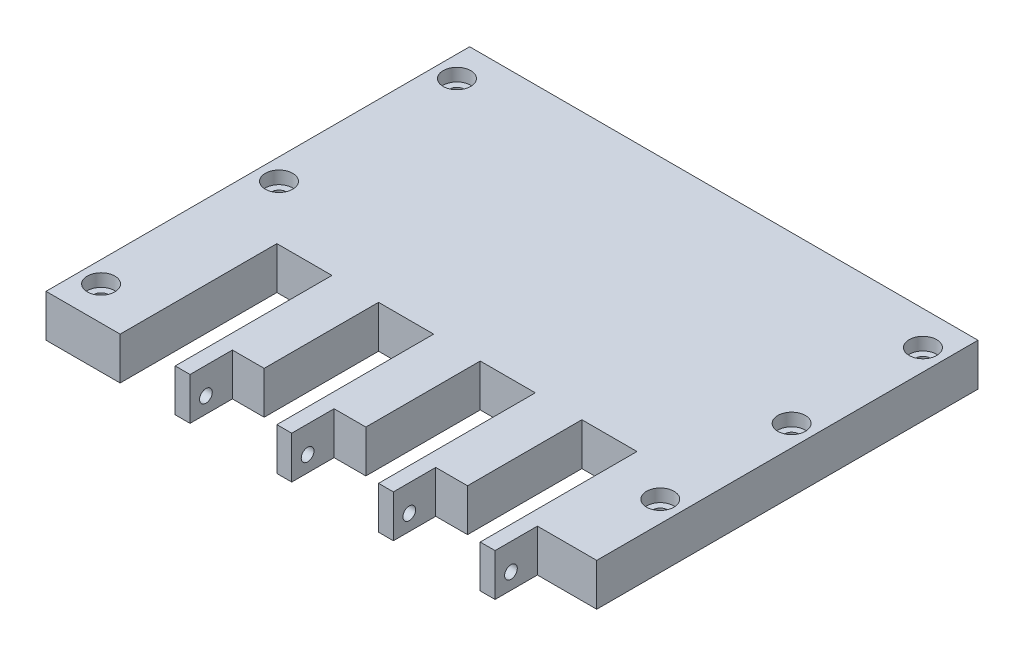
SolidWorks part; units mm, degrees
ref_plane "Front Plane" through (0, 0, 0) normal (0, 0, 1) x (1, 0, 0)
ref_plane "Top Plane" through (0, 0, 0) normal (0, 1, 0) x (1, 0, 0)
ref_plane "Right Plane" through (0, 0, 0) normal (1, 0, 0) x (0, 0, -1)
sketch "Sketch1" plane through (0, 0, 0) normal (0, 1, 0) x (1, 0, 0)
  line L1 (60, -50) -> (-60, -50)
  line L2 (60, -50) -> (60, 50)
  line L3 (60, 50) -> (-60, 50)
  line L4 (-60, -50) -> (-60, 50)
  line L5 (60, -50) -> (-60, 50) construction
  line L6 (60, 50) -> (-60, -50) construction
  point P0 (0, 0)
  dimension "D1" = 120
  dimension "D2" = 100
extrude "Boss-Extrude1" add sketch "Sketch1" along normal blind 10 contours L3 L1 | L3 L4 L1 | L3 L1 L2 region at (0, 0, 0)
sketch "Sketch2" plane through (0, 0, 50) normal (0, 0, 1) x (1, 0, 0)
  line L0 (-60, 0) -> (60, 0) construction
  line L1 (60, 10) -> (-60, 10) construction
  line L4 (-29.5, -10) -> (-42.5, -10)
  line L5 (-29.5, -10) -> (-29.5, 10)
  line L6 (-29.5, 10) -> (-42.5, 10)
  line L7 (-42.5, -10) -> (-42.5, 10)
  line L8 (-29.5, -10) -> (-42.5, 10) construction
  line L9 (-29.5, 10) -> (-42.5, -10) construction
  line L10 (-5.5, -10) -> (-18.5, -10)
  line L11 (-5.5, -10) -> (-5.5, 10)
  line L12 (-5.5, 10) -> (-18.5, 10)
  line L13 (-18.5, -10) -> (-18.5, 10)
  line L14 (-5.5, -10) -> (-18.5, 10) construction
  line L15 (-5.5, 10) -> (-18.5, -10) construction
  line L16 (18.5, -10) -> (5.5, -10)
  line L17 (18.5, -10) -> (18.5, 10)
  line L18 (18.5, 10) -> (5.5, 10)
  line L19 (5.5, -10) -> (5.5, 10)
  line L20 (18.5, -10) -> (5.5, 10) construction
  line L21 (18.5, 10) -> (5.5, -10) construction
  line L22 (42.5, -10) -> (29.5, -10)
  line L23 (42.5, -10) -> (42.5, 10)
  line L24 (42.5, 10) -> (29.5, 10)
  line L25 (29.5, -10) -> (29.5, 10)
  line L26 (42.5, -10) -> (29.5, 10) construction
  line L27 (42.5, 10) -> (29.5, -10) construction
  line L29 (60, 0) -> (-60, 0) construction
  point P7 (-36, 0)
  point P8 (-12, 0)
  point P9 (12, 0)
  point P10 (36, 0)
  point P11 (-36, 0)
  point P16 (-12, 0)
  point P21 (12, 0)
  point P26 (36, 0)
  point P33 (0, 0)
  dimension "D1" = 120
  dimension "D3" = 13
extrude "Cut-Extrude1" cut sketch "Sketch2" against normal blind 37
sketch "Sketch3" plane through (0, 0, 50) normal (0, 0, 1) x (1, 0, 0)
  line L0 (60, 10) -> (60, 0) construction
  line L1 (-18.5, 0) -> (-26, 0)
  line L2 (-18.5, 0) -> (-18.5, 10)
  line L3 (-18.5, 10) -> (-26, 10)
  line L4 (-26, 0) -> (-26, 10)
  line L5 (5.5, 0) -> (-2, 0)
  line L6 (5.5, 0) -> (5.5, 10)
  line L7 (5.5, 10) -> (-2, 10)
  line L8 (-2, 0) -> (-2, 10)
  line L9 (29.5, 0) -> (22, 0)
  line L10 (29.5, 0) -> (29.5, 10)
  line L11 (29.5, 10) -> (22, 10)
  line L12 (22, 0) -> (22, 10)
  line L13 (46, 0) -> (60, 0)
  line L14 (46, 0) -> (46, 10)
  line L15 (46, 10) -> (60, 10)
  line L16 (60, 0) -> (60, 10)
  line L17 (60, 0) -> (42.5, 0) construction
  line L18 (5.5, 10) -> (5.5, 0) construction
  line L19 (5.5, 0) -> (-5.5, 0) construction
  line L21 (-29.5, 0) -> (-29.5, 10) construction
  line L22 (-5.5, 0) -> (-5.5, 10) construction
  line L23 (42.5, 0) -> (42.5, 10) construction
  line L24 (18.5, 0) -> (18.5, 10) construction
  line L25 (-18.5, 0) -> (-5.5, 0) construction
  line L26 (-18.5, 10) -> (-18.5, 0) construction
  line L29 (-18.5, 10) -> (-29.5, 10) construction
  line L33 (5.5, 10) -> (-5.5, 10) construction
  line L34 (29.5, 10) -> (18.5, 10) construction
  line L35 (60, 10) -> (42.5, 10) construction
  dimension "D1" = 3.5
  dimension "D2" = 3.5
  dimension "D3" = 3.5
  dimension "D4" = 3.5
extrude "Cut-Extrude2" cut sketch "Sketch3" against normal blind 10
sketch "Sketch4" plane through (46, 0, 0) normal (1, 0, 0) x (0, 0, -1)
  line L1 (-40, 0) -> (-50, 0) construction
  line L2 (-50, 10) -> (-50, 0) construction
  circle A0 centre (-46.25, 3.75) radius 1.5
  dimension "D1" = 3
  dimension "D2" = 3.75
  dimension "D3" = 3.75
extrude "Cut-Extrude3" cut sketch "Sketch4" against normal up to surface (75.5 mm away) up to face at (-29.5, 5, 31.5)
hole_wizard "CBORE for M3 SHCS" positions "Sketch7" profile "Sketch8" counterbore size "M3" standard "ANSI Metric"
sketch "Sketch7" plane through (-676.2935, 10, -1323.2827) normal (0, 1, 0) x (1, 0, 0)
  line L3 (621.2935, -1281.2827) -> (621.2935, -1365.2827) construction
  line L5 (731.2935, -1281.2827) -> (731.2935, -1343.2827) construction
  circle A0 centre (731.2935, -1281.2827) radius 2.243
  circle A1 centre (731.2935, -1343.2827) radius 2.2384
  circle A3 centre (621.2935, -1281.2827) radius 2.3325
  circle A4 centre (621.2935, -1365.2827) radius 1.7576
  circle A5 centre (621.2935, -1323.2827) radius 1.8624
  circle A6 centre (731.2935, -1312.2827) radius 2.0271
  point P1 (731.2935, -1281.2827)
  point P8 (731.2935, -1343.2827)
  point P15 (621.2935, -1281.2827)
  point P17 (621.2935, -1365.2827)
  point P19 (621.2935, -1323.2827)
  point P27 (731.2935, -1312.2827)
sketch "Sketch8" plane through (55, 10, -42) normal (1, 0, 0) x (0, 0, 1)
  line L0 (0, 0) -> (0, 24.0215)
  line L1 (0, 24.0215) -> (1.7, 23)
  line L2 (1.7, 23) -> (1.7, 3)
  line L3 (1.7, 3) -> (3.25, 3)
  line L4 (3.25, 3) -> (3.25, 0)
  line L5 (3.25, 0) -> (0, 0)
  line L6 (0, 24.0215) -> (-1.7, 23) construction
  line L7 (0, -6.35) -> (0, 107.95) construction
  dimension "Hole Dia." = 3.4
  dimension "Hole Depth" = 23
  dimension "C'Bore Dia." = 6.5
  dimension "C'Bore Depth" = 3
  dimension "Drill Angle" = 118
